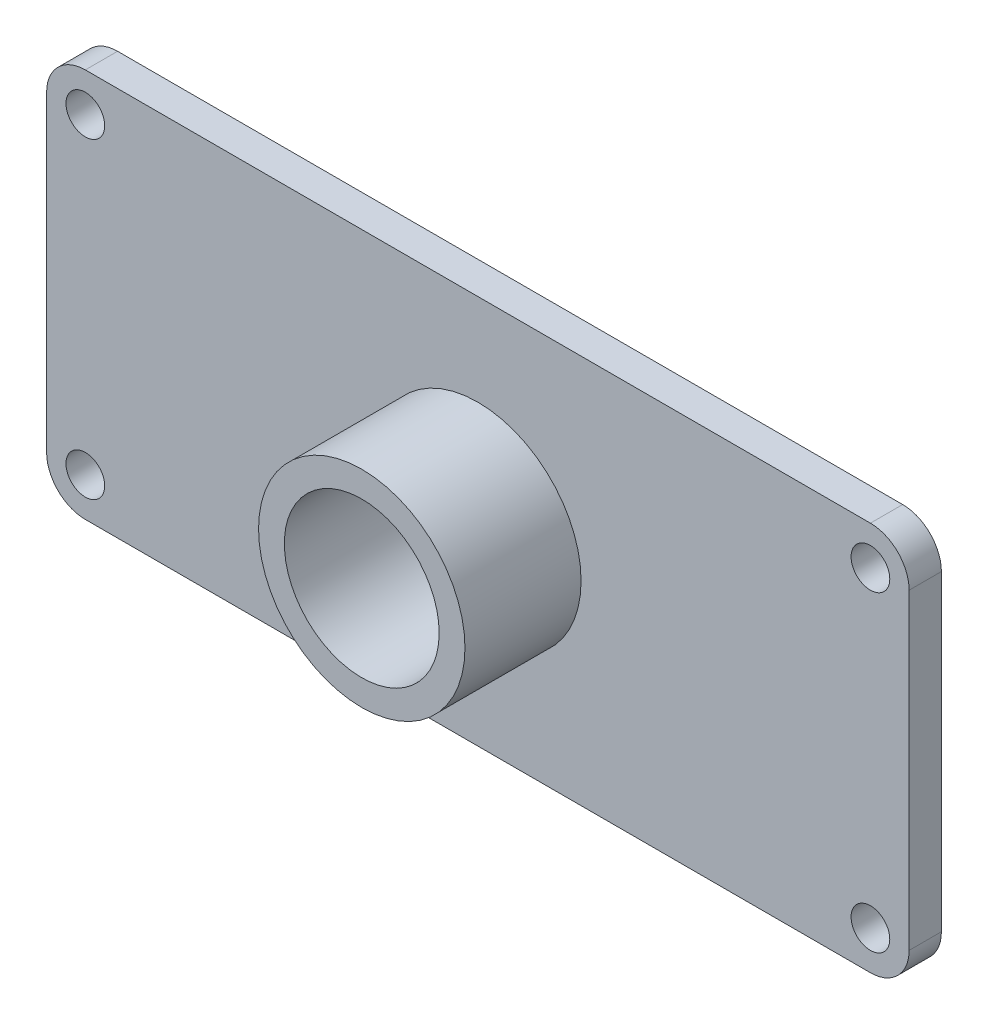
SolidWorks part; units mm, degrees
ref_plane "Front Plane" through (0, 0, 0) normal (0, 0, 1) x (1, 0, 0)
ref_plane "Top Plane" through (0, 0, 0) normal (0, 1, 0) x (1, 0, 0)
ref_plane "Right Plane" through (0, 0, 0) normal (1, 0, 0) x (0, 0, -1)
sketch "Sketch1" plane through (0, 0, 0) normal (0, 0, 1) x (1, 0, 0)
  line L1 (61568.9867, -21050.8079) -> (183274.1513, -21050.8079)
  line L2 (55568.9867, -27050.8079) -> (55568.9867, -75407.4892)
  line L3 (61568.9867, -81407.4892) -> (183274.1513, -81407.4892)
  line L4 (189274.1513, -27050.8079) -> (189274.1513, -75407.4892)
  line L5 (55568.9867, -21050.8079) -> (189274.1513, -81407.4892) construction
  line L6 (55568.9867, -81407.4892) -> (189274.1513, -21050.8079) construction
  circle A0 centre (122421.569, -51229.1486) radius 16000
  circle A1 centre (122421.569, -51229.1486) radius 12000
  arc A2 (183274.1513, -81407.4892) -> (189274.1513, -75407.4892) centre (183274.1513, -75407.4892) ccw
  arc A3 (183274.1513, -21050.8079) -> (189274.1513, -27050.8079) centre (183274.1513, -27050.8079) cw
  arc A4 (55568.9867, -75407.4892) -> (61568.9867, -81407.4892) centre (61568.9867, -75407.4892) ccw
  arc A5 (61568.9867, -21050.8079) -> (55568.9867, -27050.8079) centre (61568.9867, -27050.8079) ccw
  circle A6 centre (61568.9867, -27050.8079) radius 3000
  circle A7 centre (183274.1513, -27050.8079) radius 3000
  circle A8 centre (183274.1513, -75407.4892) radius 3000
  circle A9 centre (61568.9867, -75407.4892) radius 3000
  point P0 (122421.569, -51229.1486)
  dimension "D1" = 6000
extrude "Boss-Extrude2" add sketch "Sketch1" along normal blind 5000 contours A5 L1 A3 L4 A2 L3 A4 L2 | A1 | A6 | A9 | A7 | A8
sketch "Sketch2" plane through (0, 0, 5000) normal (0, 0, 1) x (1, 0, 0)
  circle A0 centre (122421.569, -51229.1486) radius 12000
  circle A1 centre (122421.569, -51229.1486) radius 16000
extrude "Boss-Extrude3" add sketch "Sketch2" along normal blind 18000
ref_axis "Axis1" through (122421.569, -51229.1486, 23000) along (0, 0, -1)
ref_plane "Plane1" through (8422.5202, 14588.2329, 0) normal (-0.5, -0.866, 0) x (0, 0, -1)
sketch "Sketch3" plane through (8422.5202, 14588.2329, 0) normal (-0.5, -0.866, 0) x (0, 0, -1)
  line L7 (-23141.3653, 131634.763) -> (-14123.7574, 131634.763)
  line L8 (-23000, 131634.763) -> (0, 131634.763) construction
sketch "Sketch4" plane through (8422.5202, 14588.2329, 0) normal (-0.5, -0.866, 0) x (0, 0, -1)
sketch "Sketch6" plane through (8422.5202, 14588.2329, 0) normal (-0.5, -0.866, 0) x (0, 0, -1)
  line L0 (-5000, 115634.763) -> (-14422.6712, 115634.763)
  line L1 (-23000, 115634.763) -> (-5000, 115634.763) construction
  line L2 (-14422.6712, 115634.763) -> (-5000, 86634.763)
  line L3 (-5000, 94024.0512) -> (-5000, 199423.8154) construction
  line L4 (-5000, 86634.763) -> (-5000, 115634.763)
  line L5 (-5000, 86634.763) -> (-5000, 81208.5374)
  line L6 (-5000, 61649.5581) -> (-5000, 85827.8987) construction
  line L7 (-23141.3653, 131634.763) -> (5197.2688, 131634.763)
  line L8 (-14422.6712, 147634.763) -> (-5000, 176634.763)
  line L9 (-5000, 147634.763) -> (-14422.6712, 147634.763)
  line L10 (-5000, 176634.763) -> (-5000, 147634.763)
  dimension "D1" = 45000
  dimension "D2" = 162
ref_plane "Plane3" through (8422.5202, 14588.2329, 0) normal (0.5, 0.866, 0) x (0, 0, -1)
